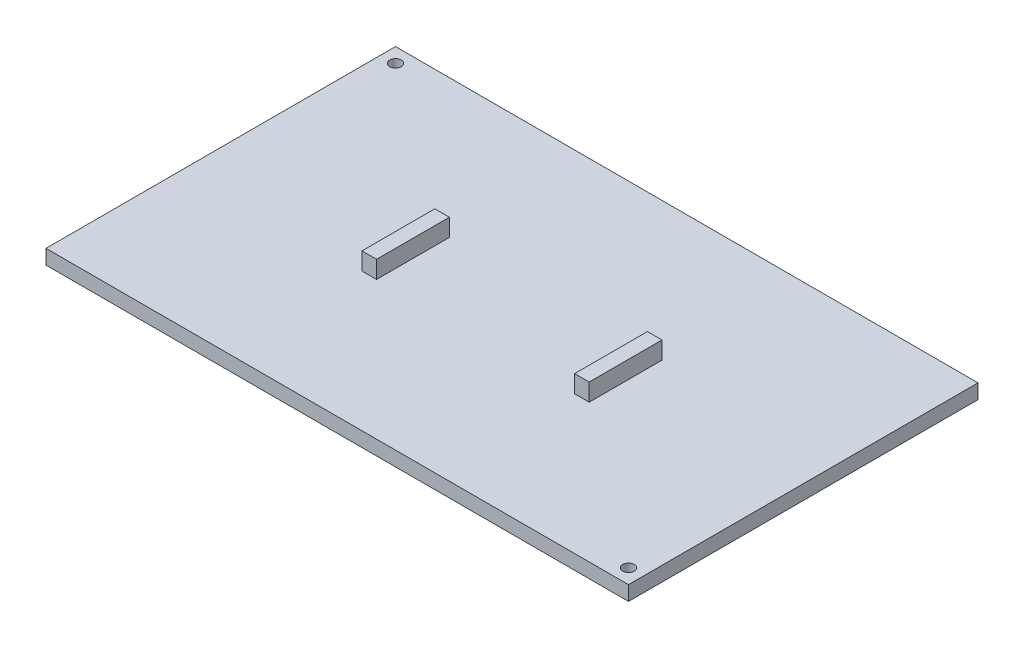
SolidWorks part; units mm, degrees
ref_plane "Front Plane" through (0, 0, 0) normal (0, 0, 1) x (1, 0, 0)
ref_plane "Top Plane" through (0, 0, 0) normal (0, 1, 0) x (1, 0, 0)
ref_plane "Right Plane" through (0, 0, 0) normal (1, 0, 0) x (0, 0, -1)
sketch "Sketch2" plane through (0, 0, 0) normal (0, 1, 0) x (1, 0, 0)
  line L0 (0, 30) -> (0, -30) construction
  line L1 (-50, 30) -> (50, 30)
  line L2 (-50, 30) -> (-50, -30)
  line L3 (-50, -30) -> (50, -30)
  line L4 (50, 30) -> (50, -30)
  point P0 (0, 0)
  dimension "D1" = 60
  dimension "D2" = 100
extrude "Boss-Extrude1" add sketch "Sketch2" along normal blind 2.5
sketch "Sketch3" plane through (0, 2.5, 0) normal (0, 1, 0) x (1, 0, 0)
  line L0 (-50, 0) -> (50, 0) construction
  line L1 (-50, 30) -> (-50, -30) construction
  line L2 (50, -30) -> (50, 30) construction
  line L3 (-25, -6.254) -> (-50, -6.254) construction
  line L4 (-50, 8.754) -> (-25, 8.754) construction
  line L5 (-25, 8.754) -> (-25, 6.254) construction
  line L6 (-25, 6.254) -> (-50, 6.254) construction
  line L7 (-25, -8.754) -> (-25, -6.254) construction
  line L8 (-50, -8.754) -> (-25, -8.754) construction
  line L9 (0, 30) -> (0, -30) construction
  line L10 (50, 30) -> (-50, 30) construction
  line L11 (-50, -30) -> (50, -30) construction
  line L12 (50, -8.754) -> (25, -8.754) construction
  line L13 (25, -8.754) -> (25, -6.254) construction
  line L14 (25, 6.254) -> (50, 6.254) construction
  line L15 (25, 8.754) -> (25, 6.254) construction
  line L16 (50, 8.754) -> (25, 8.754) construction
  line L17 (25, -6.254) -> (50, -6.254) construction
  dimension "D1" = 2.5
  dimension "D2" = 6.254
  dimension "D3" = 25
sketch "Sketch4" plane through (0, 2.5, 0) normal (0, 1, 0) x (1, 0, 0)
  line L0 (-47.5, 6.254) -> (-19.5, 6.254)
  line L1 (-19.5, 6.254) -> (-19.5, -6.254)
  line L2 (-19.5, -6.254) -> (-47.5, -6.254)
  line L3 (-47.5, -6.254) -> (-47.5, 6.254)
  line L4 (0, 30) -> (0, -30) construction
  line L5 (50, 30) -> (-50, 30) construction
  line L6 (-50, -30) -> (50, -30) construction
  line L7 (47.5, -6.254) -> (47.5, 6.254)
  line L8 (19.5, -6.254) -> (47.5, -6.254)
  line L9 (19.5, 6.254) -> (19.5, -6.254)
  line L10 (47.5, 6.254) -> (19.5, 6.254)
  line L11 (-50, 30) -> (-50, -30) construction
  line L12 (-25, 6.254) -> (-50, 6.254) construction
  line L13 (-25, -6.254) -> (-50, -6.254) construction
  dimension "D1" = 2.5
  dimension "D2" = 28
sketch "Sketch5" plane through (0, 2.5, 0) normal (0, 1, 0) x (1, 0, 0)
  line L1 (-19.5, 6.254) -> (-17, 6.254)
  line L2 (-19.5, 6.254) -> (-19.5, -6.254)
  line L3 (-19.5, -6.254) -> (-17, -6.254)
  line L4 (-17, 6.254) -> (-17, -6.254)
  line L6 (-47.5, -6.254) -> (-47.5, 6.254) construction
  line L8 (0, 30) -> (0, -30) construction
  line L9 (50, 30) -> (-50, 30) construction
  line L10 (17, 6.254) -> (17, -6.254)
  line L11 (19.5, -6.254) -> (17, -6.254)
  line L12 (19.5, 6.254) -> (19.5, -6.254)
  line L13 (19.5, 6.254) -> (17, 6.254)
  line L14 (-47.5, 6.254) -> (-19.5, 6.254) construction
  line L15 (-19.5, -6.254) -> (-47.5, -6.254) construction
  dimension "D1" = 28
  dimension "D2" = 2.5
extrude "Boss-Extrude2" add sketch "Sketch5" along normal blind 3
sketch "Sketch6" plane through (0, 2.5, 0) normal (0, 1, 0) x (1, 0, 0)
  line L1 (-50, -30) -> (50, -30) construction
  line L2 (50, 30) -> (-50, 30) construction
  line L3 (50, -30) -> (50, 30) construction
  line L4 (-50, 30) -> (-50, -30) construction
  circle A0 centre (47.5, -27.5) radius 2.5
  circle A1 centre (47.5, -27.5) radius 1
  circle A2 centre (-47.5, 27.5) radius 2.5
  circle A3 centre (-47.5, 27.5) radius 1
  dimension "D1" = 5
  dimension "D2" = 2
  dimension "D3" = 5
  dimension "D4" = 2
extrude "Cut-Extrude1" cut sketch "Sketch6" against normal blind 3 contours A1 | A3
equation "\"Width\"= 100mm"
equation "\"T\"= 2.5mm"
equation "\"D1@Sketch3\"=\"T\""
equation "\"Clear\"= 0.01in"
equation "\"D2@Sketch3\"=6+\"Clear\""
equation "\"D1@Sketch4\"=\"T\""
